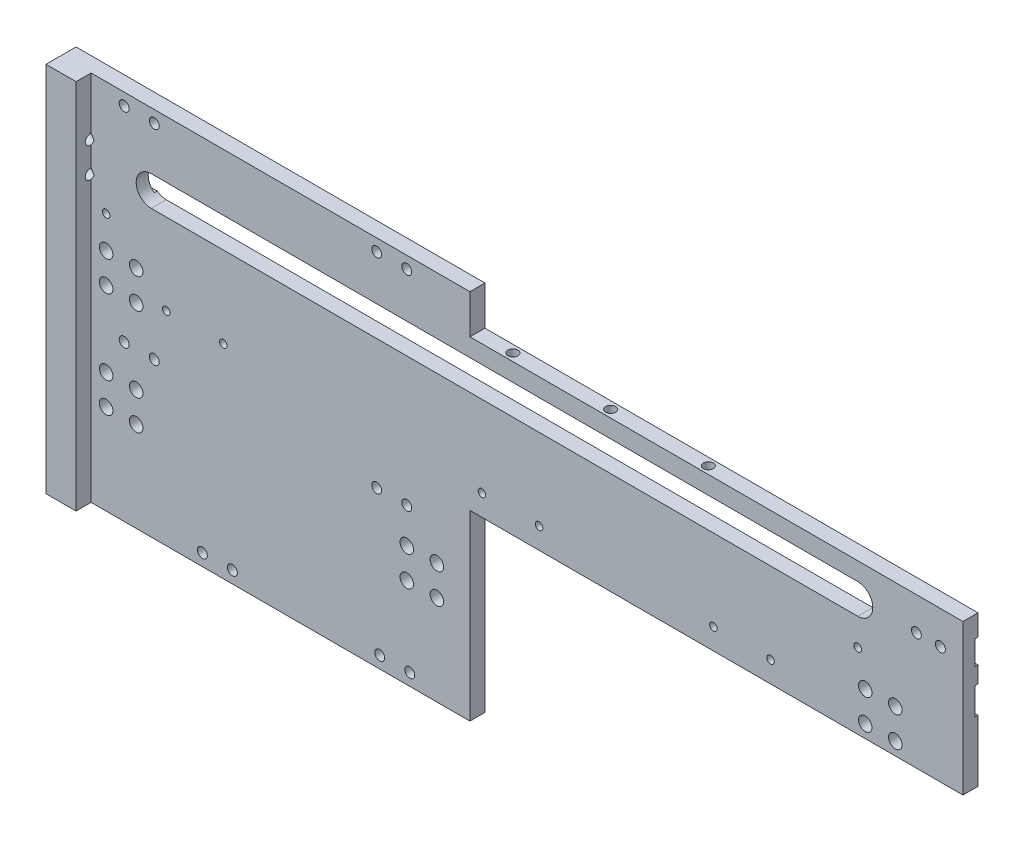
SolidWorks part; units mm, degrees
ref_plane "前视基准面" through (0, 0, 0) normal (0, 0, 1) x (1, 0, 0)
ref_plane "上视基准面" through (0, 0, 0) normal (0, 1, 0) x (1, 0, 0)
ref_plane "右视基准面" through (0, 0, 0) normal (1, 0, 0) x (0, 0, -1)
sketch "草图4" plane through (0, 0, 0) normal (0, 0, 1) x (1, 0, 0)
  line L0 (30, 99.7) -> (265, 99.7) construction
  line L1 (0, 0) -> (136, 0)
  line L2 (0, 0) -> (0, 123.7)
  line L3 (0, 123.7) -> (136, 123.7)
  line L4 (300, 60.7) -> (300, 110.7)
  line L5 (30, 104.7) -> (265, 104.7)
  line L6 (136, 123.7) -> (136, 110.7)
  line L7 (136, 110.7) -> (300, 110.7)
  line L9 (30, 94.7) -> (265, 94.7)
  line L10 (136, 0) -> (136, 60.7)
  line L11 (136, 60.7) -> (300, 60.7)
  arc A0 (30, 104.7) -> (30, 94.7) centre (30, 99.7) ccw
  arc A1 (265, 94.7) -> (265, 104.7) centre (265, 99.7) ccw
  dimension "D1" = 300
  dimension "D2" = 136
  dimension "D3" = 13
  dimension "D4" = 63
  dimension "D5" = 123.7
  dimension "D6" = 10
  dimension "D7" = 30
  dimension "D8" = 265
  dimension "D9" = 24
extrude "凸台-拉伸1" add sketch "草图4" along normal blind 10
sketch "草图5" plane through (300, 0, 0) normal (1, 0, 0) x (0, 0, -1)
  line L1 (0, 60.7) -> (0, 110.7) construction
  line L2 (-10, 123.7) -> (0, 123.7) construction
  line L3 (0, 103.7) -> (-1, 103.7)
  line L4 (0, 103.7) -> (0, 95.7)
  line L6 (0, 95.7) -> (-1, 95.7)
  line L7 (0, 90.2) -> (-1, 90.2)
  line L8 (0, 90.2) -> (0, 81.2)
  line L9 (0, 81.2) -> (-1, 81.2)
  line L10 (-1, 90.2) -> (-1, 81.2)
  line L12 (-1, 103.7) -> (-1, 95.7)
  dimension "D1" = 20
  dimension "D2" = 8
  dimension "D3" = 33.5
  dimension "D4" = 9
  dimension "D5" = 1
extrude "切除-拉伸1" cut sketch "草图5" against normal through all
hole_wizard "M4 螺纹孔1" positions "草图6" profile "草图7" tap size "M4" standard "ISO"
sketch "草图6" plane through (0, 0, 0) normal (-1, 0, 0) x (0, 0, 1)
  line L0 (10, 123.7) -> (10, 0) construction
  line L1 (10, 123.7) -> (0, 123.7) construction
  point P0 (5.304, 104.7)
  point P2 (5.304, 94.7)
  dimension "D1" = 4.696
  dimension "D2" = 19
  dimension "D3" = 29
sketch "草图7" plane through (0, 104.7, 5.304) normal (0, 1, 0) x (0, 0, 1)
  line L0 (0, 0) -> (0, 11.0914)
  line L1 (0, 11.0914) -> (1.65, 10.1)
  line L2 (1.65, 10.1) -> (1.65, 0)
  line L5 (1.65, 0) -> (0, 0)
  line L10 (0, 11.0914) -> (-1.65, 10.1) construction
  line L11 (0, -6.35) -> (0, 107.95) construction
  dimension "螺纹孔钻头直径" = 3.3
  dimension "螺纹孔钻头深度" = 10.1
  dimension "导头角度" = 118
cosmetic thread "孔螺蚊线1" parameters "D1"=8, "D2"=4
cosmetic thread "孔螺蚊线2" parameters "D1"=8, "D2"=4
sketch "草图8" plane through (0, 0, 10) normal (0, 0, 1) x (1, 0, 0)
  line L1 (136, 123.7) -> (0, 123.7) construction
  line L2 (10, 123.7) -> (316.5249, 123.7)
  line L3 (10, 123.7) -> (10, -39.0626)
  line L4 (10, -39.0626) -> (316.5249, -39.0626)
  line L5 (316.5249, 123.7) -> (316.5249, -39.0626)
  line L6 (0, 123.7) -> (0, 0) construction
  dimension "D1" = 10
extrude "切除-拉伸2" cut sketch "草图8" against normal blind 5
hole_wizard "M4 螺纹孔2" positions "草图9" profile "草图10" tap size "M4" standard "ISO"
sketch "草图9" plane through (0, 0, 5) normal (0, 0, 1) x (1, 0, 0)
  line L0 (136, 123.7) -> (10, 123.7) construction
  line L1 (0, 123.7) -> (0, 0) construction
  point P0 (21, 119.7)
  point P2 (31, 119.7)
  point P4 (105, 119.7)
  point P6 (115, 119.7)
  point P8 (21, 51.7)
  point P10 (31, 51.7)
  point P12 (105, 51.7)
  point P14 (115, 51.7)
  point P16 (47, 4)
  point P18 (57, 4)
  point P20 (106, 4)
  point P22 (116, 4)
  dimension "D1" = 4
  dimension "D2" = 72
  dimension "D3" = 119.7
  dimension "D4" = 21
  dimension "D5" = 31
  dimension "D6" = 105
  dimension "D7" = 115
  dimension "D8" = 47
  dimension "D9" = 57
  dimension "D10" = 106
  dimension "D11" = 116
sketch "草图10" plane through (21, 119.7, 5) normal (1, 0, 0) x (0, -1, 0)
  line L0 (0, 0) -> (0, 11.0914)
  line L1 (0, 11.0914) -> (1.65, 10.1)
  line L2 (1.65, 10.1) -> (1.65, 0)
  line L5 (1.65, 0) -> (0, 0)
  line L10 (0, 11.0914) -> (-1.65, 10.1) construction
  line L11 (0, -6.35) -> (0, 107.95) construction
  dimension "螺纹孔钻头直径" = 3.3
  dimension "螺纹孔钻头深度" = 10.1
  dimension "导头角度" = 118
cosmetic thread "孔螺蚊线3" parameters "D1"=5, "D2"=4
cosmetic thread "孔螺蚊线4" parameters "D1"=5, "D2"=4
cosmetic thread "孔螺蚊线5" parameters "D1"=5, "D2"=4
cosmetic thread "孔螺蚊线6" parameters "D1"=5, "D2"=4
cosmetic thread "孔螺蚊线7" parameters "D1"=5, "D2"=4
cosmetic thread "孔螺蚊线8" parameters "D1"=5, "D2"=4
cosmetic thread "孔螺蚊线9" parameters "D1"=5, "D2"=4
cosmetic thread "孔螺蚊线10" parameters "D1"=5, "D2"=4
cosmetic thread "孔螺蚊线11" parameters "D1"=5, "D2"=4
cosmetic thread "孔螺蚊线12" parameters "D1"=5, "D2"=4
cosmetic thread "孔螺蚊线13" parameters "D1"=5, "D2"=4
cosmetic thread "孔螺蚊线14" parameters "D1"=5, "D2"=4
hole_wizard "M3 螺纹孔1" positions "草图11" profile "草图12" tap size "M3" standard "ISO"
sketch "草图11" plane through (0, 0, 5) normal (0, 0, 1) x (1, 0, 0)
  line L0 (0, 123.7) -> (0, 0) construction
  line L1 (10, 123.7) -> (0, 123.7) construction
  point P0 (15, 85.7)
  point P2 (265, 85.7)
  dimension "D1" = 15
  dimension "D2" = 265
  dimension "D3" = 38
sketch "草图12" plane through (15, 85.7, 5) normal (1, 0, 0) x (0, -1, 0)
  line L0 (0, 0) -> (0, 8.2511)
  line L1 (0, 8.2511) -> (1.25, 7.5)
  line L2 (1.25, 7.5) -> (1.25, 0)
  line L5 (1.25, 0) -> (0, 0)
  line L10 (0, 8.2511) -> (-1.25, 7.5) construction
  line L11 (0, -6.35) -> (0, 107.95) construction
  dimension "螺纹孔钻头直径" = 2.5
  dimension "螺纹孔钻头深度" = 7.5
  dimension "导头角度" = 118
cosmetic thread "孔螺蚊线15" parameters "D1"=4, "D2"=3
cosmetic thread "孔螺蚊线16" parameters "D1"=4, "D2"=3
hole_wizard "M3 螺纹孔2" positions "草图13" profile "草图14" tap size "M3" standard "ISO"
sketch "草图13" plane through (0, 0, 5) normal (0, 0, 1) x (1, 0, 0)
  line L0 (136, 123.7) -> (10, 123.7) construction
  line L1 (0, 123.7) -> (0, 0) construction
  point P0 (35, 67.7)
  point P2 (54, 67.7)
  point P4 (140, 67.7)
  point P6 (159, 67.7)
  point P8 (217, 67.7)
  point P10 (236, 67.7)
  dimension "D1" = 56
  dimension "D2" = 35
  dimension "D3" = 54
  dimension "D4" = 140
  dimension "D5" = 159
  dimension "D6" = 217
  dimension "D7" = 236
sketch "草图14" plane through (35, 67.7, 5) normal (1, 0, 0) x (0, -1, 0)
  line L0 (0, 0) -> (0, 8.2511)
  line L1 (0, 8.2511) -> (1.25, 7.5)
  line L2 (1.25, 7.5) -> (1.25, 0)
  line L5 (1.25, 0) -> (0, 0)
  line L10 (0, 8.2511) -> (-1.25, 7.5) construction
  line L11 (0, -6.35) -> (0, 107.95) construction
  dimension "螺纹孔钻头直径" = 2.5
  dimension "螺纹孔钻头深度" = 7.5
  dimension "导头角度" = 118
cosmetic thread "孔螺蚊线17" parameters "D1"=5, "D2"=3
cosmetic thread "孔螺蚊线18" parameters "D1"=5, "D2"=3
cosmetic thread "孔螺蚊线19" parameters "D1"=5, "D2"=3
cosmetic thread "孔螺蚊线20" parameters "D1"=5, "D2"=3
cosmetic thread "孔螺蚊线21" parameters "D1"=5, "D2"=3
cosmetic thread "孔螺蚊线22" parameters "D1"=5, "D2"=3
sketch "草图15" plane through (0, 0, 5) normal (0, 0, 1) x (1, 0, 0)
  line L0 (0, 123.7) -> (0, 0) construction
  line L1 (136, 123.7) -> (10, 123.7) construction
  line L2 (20, 75) -> (20, 133.6461) construction
  line L3 (4.9076, 70) -> (26.7652, 70) construction
  circle A0 centre (15, 75) radius 2.25
  circle A1 centre (25, 75) radius 2.25
  circle A2 centre (25, 65) radius 2.25
  circle A3 centre (15, 65) radius 2.25
  dimension "D1" = 4.5
  dimension "D2" = 15
  dimension "D3" = 48.7
  dimension "D4" = 5
  dimension "D5" = 5
extrude "切除-拉伸3" cut sketch "草图15" against normal blind 5
pattern_linear "阵列(线性)1" count 2 spacing 252.5 along (1, 0, 0) of "切除-拉伸3"
pattern_linear "阵列(线性)2" count 2 spacing 35 along (0, -1, 0) of "切除-拉伸3"
pattern_linear "阵列(线性)3" count 2 spacing 100 along (1, 0, 0) of "阵列(线性)2"
sketch "草图16" plane through (0, 0, 5) normal (0, 0, 1) x (1, 0, 0)
  line L1 (105.3882, 81.0569) -> (130.1902, 81.0569)
  line L2 (105.3882, 81.0569) -> (105.3882, 58.9705)
  line L3 (105.3882, 58.9705) -> (130.1902, 58.9705)
  line L4 (130.1902, 81.0569) -> (130.1902, 58.9705)
extrude "凸台-拉伸2" add sketch "草图16" against normal up to surface (5 mm away) up to face at (122.75, 75, 0)
hole_wizard "M4 螺纹孔3" positions "草图17" profile "草图18" tap size "M4" standard "ISO"
sketch "草图17" plane through (0, 60.7, 0) normal (0, -1, 0) x (-1, 0, 0)
  line L0 (-136, -5) -> (-300, -5) construction
  line L1 (0, -10) -> (0, 0) construction
  point P0 (-147.8, -2.5)
  point P2 (-180.3, -2.5)
  point P4 (-212.8, -2.5)
  dimension "D1" = 2.5
  dimension "D2" = 147.8
  dimension "D3" = 180.3
  dimension "D4" = 212.8
sketch "草图18" plane through (147.8, 60.7, 2.5) normal (1, 0, 0) x (0, 0, -1)
  line L0 (0, 0) -> (0, 11.0914)
  line L1 (0, 11.0914) -> (1.65, 10.1)
  line L2 (1.65, 10.1) -> (1.65, 0)
  line L5 (1.65, 0) -> (0, 0)
  line L10 (0, 11.0914) -> (-1.65, 10.1) construction
  line L11 (0, -6.35) -> (0, 107.95) construction
  dimension "螺纹孔钻头直径" = 3.3
  dimension "螺纹孔钻头深度" = 10.1
  dimension "导头角度" = 118
cosmetic thread "孔螺蚊线23" parameters "D1"=8, "D2"=4
cosmetic thread "孔螺蚊线24" parameters "D1"=8, "D2"=4
cosmetic thread "孔螺蚊线25" parameters "D1"=8, "D2"=4
ref_plane "基准面1" through (0, 85.7, 0) normal (0, -1, 0) x (-1, 0, 0)
mirror "镜向1" about plane through (0, 85.7, 0) normal (0, -1, 0) of "M4 螺纹孔3"
hole_wizard "M4 螺纹孔4" positions "草图19" profile "草图20" tap size "M4" standard "ISO"
sketch "草图19" plane through (0, 0, 1) normal (0, 0, -1) x (-1, 0, 0)
  line L0 (-300, 103.7) -> (-300, 95.7) construction
  line L1 (-268, 95.7) -> (-300, 95.7) construction
  point P0 (-284.5, 99.7)
  point P2 (-292.5, 99.7)
  dimension "D1" = 8
  dimension "D2" = 7.5
  dimension "D3" = 4
sketch "草图20" plane through (284.5, 99.7, 1) normal (1, 0, 0) x (0, 1, 0)
  line L0 (0, 0) -> (0, 11.0914)
  line L1 (0, 11.0914) -> (1.65, 10.1)
  line L2 (1.65, 10.1) -> (1.65, 0)
  line L5 (1.65, 0) -> (0, 0)
  line L10 (0, 11.0914) -> (-1.65, 10.1) construction
  line L11 (0, -6.35) -> (0, 107.95) construction
  dimension "螺纹孔钻头直径" = 3.3
  dimension "螺纹孔钻头深度" = 10.1
  dimension "导头角度" = 118
cosmetic thread "孔螺蚊线26" parameters "D1"=4, "D2"=4
cosmetic thread "孔螺蚊线27" parameters "D1"=4, "D2"=4
